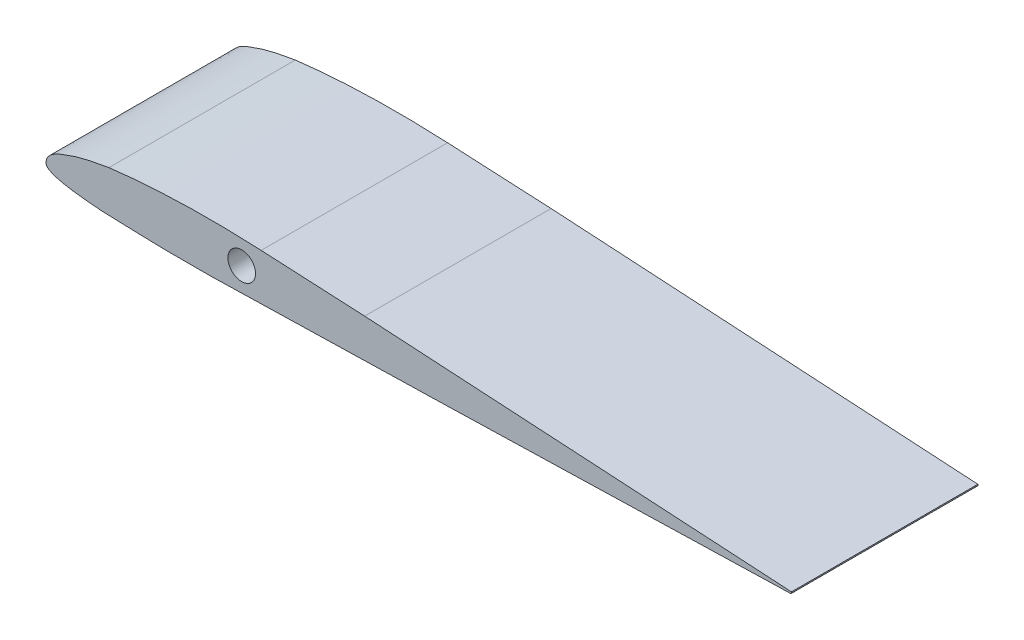
SolidWorks part; units mm, degrees
material "1.3# EPP"
ref_plane "Front Plane" through (0, 0, 0) normal (0, 0, 1) x (1, 0, 0)
ref_plane "Top Plane" through (0, 0, 0) normal (0, 1, 0) x (1, 0, 0)
ref_plane "Right Plane" through (0, 0, 0) normal (1, 0, 0) x (0, 0, -1)
sketch "Sketch3" plane through (0, 0, 0) normal (0, 0, 1) x (1, 0, 0)
  line L0 (202.9941, 8.6587) -> (110.5837, 6.1553)
  line L1 (110.5837, 6.1553) -> (45.2437, 4.5477)
  line L2 (58.6413, 17.491) -> (86.8465, 16.0766)
  line L3 (0, 35.3471) -> (0, -15.2378) construction
  line L4 (86.8465, 16.0766) -> (160.9786, 11.667)
  line L5 (160.9786, 11.667) -> (203.1607, 9.1578)
  line L6 (203.1999, 14.8061) -> (203.1999, -9.9364) construction
  line L7 (0, 0) -> (203.1999, 0) construction
  line L8 (50.8, 72.9775) -> (50.8, -63.9956) construction
  arc A0 (203.1607, 9.1578) -> (202.9941, 8.6587) centre (202.8278, 8.9915) cw
  spline S0 degree 3 poles (45.2437, 4.5477) (38.9236, 4.5689) (32.5987, 4.4374) (26.2837, 4.6938) (22.3484, 4.8536) (18.4102, 4.9373) (14.4749, 5.0971) (14.4129, 5.0996) (14.3701, 5.1734) (14.3085, 5.1801) (13.7572, 5.24) (0.0923, 5.9331) (0.0016, 8.7406) (-0.0833, 11.3694) (3.2406, 12.5979) (5.1525, 13.3198) (6.7026, 13.905) (8.2818, 14.4263) (9.8909, 14.8216) (12.2626, 15.4044) (14.6912, 15.8835) (17.1496, 16.275) knots 0 0 0 0 1 1 1 2 2 2 3 3 3 4 4 4 5 5 5 6 6 6 6.272168 6.272168 6.272168 6.272168
  spline S1 degree 3 poles (17.1496, 16.275) (28.8325, 17.7257) (42.6703, 18.2919) (58.6413, 17.491) knots 0 0 0 0 1 1 1 1
  point P17 (50.8, 17.7806)
  point P18 (50.8, 4.6844)
  dimension "D1" = 203.1999
  dimension "D2" = 50.8
extrude "Airfoil" add sketch "Sketch3" along normal blind 50.8
sketch "Sketch8" plane through (0, 0, 0) normal (0, 0, -1) x (-1, 0, 0)
  line L0 (0, 16.6795) -> (0, -1.637) construction
  line L1 (-203.1999, 12.5809) -> (-203.1999, 6.3994) construction
  line L2 (-53.34, 11.2284) -> (-53.34, 17.7099) construction
  line L3 (-53.34, 11.2284) -> (-53.34, 4.7469) construction
  line L4 (-45.2437, 4.5477) -> (-110.5837, 6.1553) construction
  circle A0 centre (-53.34, 11.2284) radius 3.7592
  arc A1 (-203.1607, 9.1578) -> (-202.9941, 8.6587) centre (-202.8278, 8.9915) ccw construction
  spline S0 degree 3 poles (-17.1496, 16.275) (-14.6912, 15.8835) (-12.2626, 15.4044) (-9.8909, 14.8216) (-8.2818, 14.4263) (-6.7026, 13.905) (-5.1525, 13.3198) (-3.2406, 12.5979) (0.0833, 11.3694) (-0.0016, 8.7406) (-0.0923, 5.9331) (-13.7572, 5.24) (-14.3085, 5.1801) (-14.3701, 5.1734) (-14.4129, 5.0996) (-14.4749, 5.0971) (-18.4102, 4.9373) (-22.3484, 4.8536) (-26.2837, 4.6938) (-32.5987, 4.4374) (-38.9236, 4.5689) (-45.2437, 4.5477) knots 0 0 0 0 0.272168 0.272168 0.272168 1.272168 1.272168 1.272168 2.272168 2.272168 2.272168 3.272168 3.272168 3.272168 4.272168 4.272168 4.272168 5.272168 5.272168 5.272168 6.272168 6.272168 6.272168 6.272168 construction
  spline S1 degree 3 poles (-58.6413, 17.491) (-42.6703, 18.2919) (-28.8325, 17.7257) (-17.1496, 16.275) knots 0 0 0 0 1 1 1 1 construction
  dimension "D1" = 7.5184
  dimension "D2" = 53.34
extrude "Camera Channel" cut sketch "Sketch8" against normal up to next
